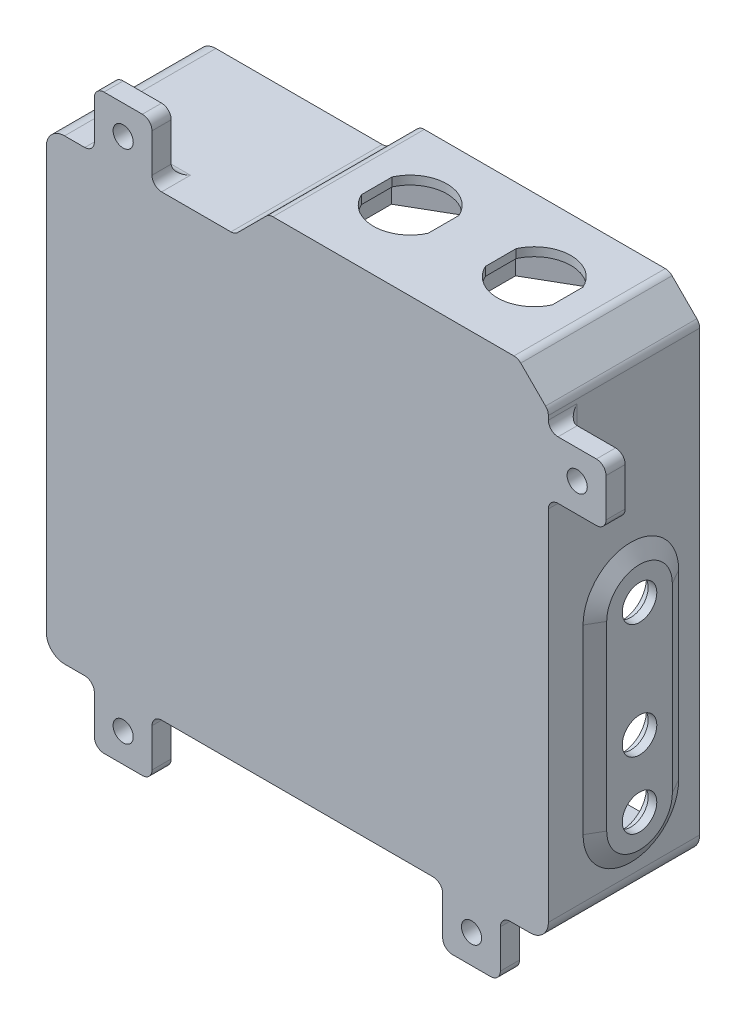
SolidWorks part; units mm, degrees
ref_plane "Front Plane" through (0, 0, 0) normal (0, 0, 1) x (1, 0, 0)
ref_plane "Top Plane" through (0, 0, 0) normal (0, 1, 0) x (1, 0, 0)
ref_plane "Right Plane" through (0, 0, 0) normal (1, 0, 0) x (0, 0, -1)
sketch "Sketch1" plane through (0, 0, 0) normal (0, 0, 1) x (1, 0, 0)
  line L9 (-68.5151, 31.874) -> (-68.5151, -49.766)
  line L10 (-31.5951, 31.874) -> (22.4049, 31.874)
  line L11 (22.4049, 31.874) -> (22.4049, -31.776)
  line L12 (22.4049, -31.776) -> (22.4049, -46.156)
  line L13 (22.4049, -46.156) -> (22.4049, -49.766)
  line L14 (-31.5951, -49.766) -> (-68.5151, -49.766)
  line L15 (22.4049, -49.766) -> (-31.5951, -49.766)
  line L16 (-31.5951, 36.874) -> (25.4049, 36.874)
  line L17 (-68.5151, 31.874) -> (-31.5951, 31.874)
  line L18 (27.4049, 34.874) -> (27.4049, -31.776)
  line L19 (27.4049, -31.776) -> (27.4049, -46.156)
  line L20 (27.4049, -46.156) -> (27.4049, -52.766)
  line L21 (25.4049, -54.766) -> (-31.5951, -54.766)
  line L22 (-31.5951, -54.766) -> (-71.5151, -54.766)
  line L23 (-73.5151, 34.874) -> (-73.5151, -52.766)
  line L24 (-71.5151, 36.874) -> (-31.5951, 36.874)
  line L25 (-31.5951, 36.874) -> (27.4049, 36.874) construction
  line L26 (27.4049, 36.874) -> (27.4049, -31.776) construction
  line L27 (27.4049, -46.156) -> (27.4049, -54.766) construction
  line L28 (27.4049, -54.766) -> (-31.5951, -54.766) construction
  line L29 (-31.5951, -54.766) -> (-73.5151, -54.766) construction
  line L30 (-73.5151, 36.874) -> (-73.5151, -54.766) construction
  line L31 (-73.5151, 36.874) -> (-31.5951, 36.874) construction
  line L32 (-71.5151, 38.674) -> (-31.5951, 38.674)
  line L33 (-31.5951, 38.674) -> (25.4049, 38.674)
  line L34 (29.2049, 34.874) -> (29.2049, -31.776)
  line L35 (29.2049, -31.776) -> (29.2049, -46.156)
  line L36 (29.2049, -46.156) -> (29.2049, -52.766)
  line L37 (25.4049, -56.566) -> (-31.5951, -56.566)
  line L38 (-31.5951, -56.566) -> (-71.5151, -56.566)
  line L39 (-75.3151, 34.874) -> (-75.3151, -52.766)
  arc A0 (25.4049, 36.874) -> (27.4049, 34.874) centre (25.4049, 34.874) cw
  arc A1 (27.4049, -52.766) -> (25.4049, -54.766) centre (25.4049, -52.766) cw
  arc A2 (-71.5151, -54.766) -> (-73.5151, -52.766) centre (-71.5151, -52.766) cw
  arc A3 (-73.5151, 34.874) -> (-71.5151, 36.874) centre (-71.5151, 34.874) cw
  arc A4 (25.4049, 38.674) -> (29.2049, 34.874) centre (25.4049, 34.874) cw
  arc A5 (29.2049, -52.766) -> (25.4049, -56.566) centre (25.4049, -52.766) cw
  arc A6 (-71.5151, -56.566) -> (-75.3151, -52.766) centre (-71.5151, -52.766) cw
  arc A7 (-75.3151, 34.874) -> (-71.5151, 38.674) centre (-71.5151, 34.874) cw
  dimension "D2" = 2
  dimension "D1" = 5
  dimension "D3" = 1.8
extrude "Boss-Extrude1" add sketch "Sketch1" along normal blind 1.5 contours L32 L33 A4 L34 L35 L36 A5 L37 L38 A6 L39 A7
sketch "Sketch2" plane through (0, 0, 1.5) normal (0, 0, 1) x (1, 0, 0)
  line L9 (-22.7084, 43.974) -> (-22.7084, 50.974)
  line L10 (-9.2084, 43.974) -> (-9.2084, 50.974)
  line L11 (3.1216, 43.974) -> (3.1216, 50.974)
  line L12 (16.6216, 43.974) -> (16.6216, 50.974)
  line L13 (18.8716, 41.674) -> (18.8716, 38.674)
  line L14 (0.8716, 41.674) -> (0.8716, 38.674)
  line L15 (-6.9584, 41.674) -> (-6.9584, 38.674)
  line L16 (-24.9584, 41.674) -> (-24.9584, 38.674)
  line L17 (-71.5151, 38.674) -> (25.4049, 38.674)
  line L18 (-22.7084, 43.974) -> (-24.9584, 43.974)
  line L19 (-24.9584, 43.974) -> (-24.9584, 41.674)
  line L20 (-9.2084, 43.974) -> (-6.9584, 43.974)
  line L21 (-6.9584, 43.974) -> (-6.9584, 41.674)
  line L22 (3.1216, 43.974) -> (0.8716, 43.974)
  line L23 (0.8716, 43.974) -> (0.8716, 41.674)
  line L24 (16.6216, 43.974) -> (18.8716, 43.974)
  line L25 (18.8716, 43.974) -> (18.8716, 41.674)
  line L26 (-22.7084, 45.774) -> (-24.9584, 45.774)
  line L27 (-9.2084, 45.774) -> (-6.9584, 45.774)
  line L28 (3.1216, 45.774) -> (0.8716, 45.774)
  line L29 (16.6216, 45.774) -> (18.8716, 45.774)
  line L30 (-24.9584, 45.774) -> (-28.9584, 45.774)
  line L31 (-28.9584, 45.774) -> (-36.0584, 38.674)
  line L32 (18.8716, 45.774) -> (22.8716, 45.774)
  line L33 (29.2049, 34.874) -> (29.2049, -52.766) construction
  line L34 (29.2049, 34.874) -> (29.2049, -52.766)
  line L35 (29.2049, 34.874) -> (29.2049, 39.4408)
  line L36 (-22.7084, 45.774) -> (-9.2084, 45.774)
  line L37 (22.8716, 45.774) -> (29.2049, 39.4408)
  line L38 (-6.9584, 45.774) -> (0.8716, 45.774)
  line L39 (3.1216, 45.774) -> (16.6216, 45.774)
  arc M10 (29.2049, 34.874) -> (25.4049, 38.674) centre (25.4049, 34.874) ccw
  line M11 (25.4049, 38.674) -> (-71.5151, 38.674)
  dimension "D1" = 1.8
  dimension "D2" = 1.8
  dimension "D3" = 1.8
  dimension "D4" = 1.8
extrude "Boss-Extrude2" add sketch "Sketch2" against normal blind 1.5 separate body contours L30 L31 L16 L19 L18 L9 L26 M11 | L36 L9 L18 L19 L16 L15 L21 L20 L10 M11 | L38 L27 L10 L20 L21 L15 L14 L23 L22 L11 L28 M11 | L39 L11 L22 L23 L14 L13 L25 L24 L12 M11 | L37 L32 L29 L12 L24 L25 L13 L35 M11 M10 region at (-28.6478, 41.8928, 1.5) region at (-15.9584, 42.0447, 1.5) region at (-3.0434, 42.561, 1.5) region at (9.8716, 42.0447, 1.5) region at (22.8246, 41.6987, 1.5)
fillet "Fillet1" radius 2 4 edges at (22.8716, 45.774, 0.75) (29.2049, 39.4408, 0.75) (-28.9584, 45.774, 0.75) (-36.0584, 38.674, 0.75)
sketch "Sketch3" plane through (0, 0, 0) normal (0, 0, -1) x (-1, 0, 0)
  line L0 (-29.2049, 38.6123) -> (-29.2049, -52.766) construction
  line L1 (-23.4574, 45.1882) -> (-28.6191, 40.0265) construction
  line L2 (-22.0432, 45.774) -> (28.1299, 45.774) construction
  line L3 (29.5442, 45.1882) -> (35.4726, 39.2598) construction
  line L4 (71.5151, 38.674) -> (36.8868, 38.674) construction
  line L5 (75.3151, 34.874) -> (75.3151, -52.766) construction
  line L6 (-25.4049, -56.566) -> (71.5151, -56.566) construction
  line L7 (-29.2049, 38.6123) -> (-29.2049, -52.766)
  line L8 (-23.4574, 45.1882) -> (-28.6191, 40.0265)
  line L9 (-22.0432, 45.774) -> (28.1299, 45.774)
  line L10 (29.5442, 45.1882) -> (35.4726, 39.2598)
  line L11 (71.5151, 38.674) -> (36.8868, 38.674)
  line L12 (75.3151, 34.874) -> (75.3151, -52.766)
  line L13 (-25.4049, -56.566) -> (71.5151, -56.566)
  line L14 (-25.4049, -54.766) -> (71.5151, -54.766)
  line L15 (73.5151, 34.874) -> (73.5151, -52.766)
  line L16 (71.5151, 36.874) -> (36.8868, 36.874)
  line L17 (28.2714, 43.9154) -> (34.1998, 37.987)
  line L18 (-22.0432, 43.974) -> (28.1299, 43.974)
  line L19 (-22.1846, 43.9154) -> (-27.3463, 38.7538)
  line L20 (-27.4049, 38.6123) -> (-27.4049, -52.766)
  arc A0 (-29.2049, -52.766) -> (-25.4049, -56.566) centre (-25.4049, -52.766) ccw construction
  arc A1 (-28.6191, 40.0265) -> (-29.2049, 38.6123) centre (-27.2049, 38.6123) ccw construction
  arc A2 (-22.0432, 45.774) -> (-23.4574, 45.1882) centre (-22.0432, 43.774) ccw construction
  arc A3 (29.5442, 45.1882) -> (28.1299, 45.774) centre (28.1299, 43.774) ccw construction
  arc A4 (35.4726, 39.2598) -> (36.8868, 38.674) centre (36.8868, 40.674) ccw construction
  arc A5 (75.3151, 34.874) -> (71.5151, 38.674) centre (71.5151, 34.874) ccw construction
  arc A6 (71.5151, -56.566) -> (75.3151, -52.766) centre (71.5151, -52.766) ccw construction
  arc A7 (-29.2049, -52.766) -> (-25.4049, -56.566) centre (-25.4049, -52.766) ccw
  arc A8 (-28.6191, 40.0265) -> (-29.2049, 38.6123) centre (-27.2049, 38.6123) ccw
  arc A9 (-22.0432, 45.774) -> (-23.4574, 45.1882) centre (-22.0432, 43.774) ccw
  arc A10 (29.5442, 45.1882) -> (28.1299, 45.774) centre (28.1299, 43.774) ccw
  arc A11 (35.4726, 39.2598) -> (36.8868, 38.674) centre (36.8868, 40.674) ccw
  arc A12 (75.3151, 34.874) -> (71.5151, 38.674) centre (71.5151, 34.874) ccw
  arc A13 (71.5151, -56.566) -> (75.3151, -52.766) centre (71.5151, -52.766) ccw
  arc A14 (71.5151, -54.766) -> (73.5151, -52.766) centre (71.5151, -52.766) ccw
  arc A15 (73.5151, 34.874) -> (71.5151, 36.874) centre (71.5151, 34.874) ccw
  arc A16 (34.1998, 37.987) -> (36.8868, 36.874) centre (36.8868, 40.674) ccw
  arc A17 (28.2714, 43.9154) -> (28.1299, 43.974) centre (28.1299, 43.774) ccw
  arc A18 (-22.0432, 43.974) -> (-22.1846, 43.9154) centre (-22.0432, 43.774) ccw
  arc A19 (-27.3463, 38.7538) -> (-27.4049, 38.6123) centre (-27.2049, 38.6123) ccw
  arc A20 (-27.4049, -52.766) -> (-25.4049, -54.766) centre (-25.4049, -52.766) ccw
  line M2 (28.1299, 45.774) -> (-22.0432, 45.774)
  arc M3 (-22.0432, 45.774) -> (-23.4574, 45.1882) centre (-22.0432, 43.774) ccw
  line M4 (-23.4574, 45.1882) -> (-28.6191, 40.0265)
  arc M5 (-28.6191, 40.0265) -> (-29.2049, 38.6123) centre (-27.2049, 38.6123) ccw
  line M6 (-29.2049, 38.6123) -> (-29.2049, -52.766)
  arc M7 (-29.2049, -52.766) -> (-25.4049, -56.566) centre (-25.4049, -52.766) ccw
  line M8 (-25.4049, -56.566) -> (71.5151, -56.566)
  arc M9 (71.5151, -56.566) -> (75.3151, -52.766) centre (71.5151, -52.766) ccw
  line M10 (75.3151, -52.766) -> (75.3151, 34.874)
  arc M11 (75.3151, 34.874) -> (71.5151, 38.674) centre (71.5151, 34.874) ccw
  line M12 (71.5151, 38.674) -> (36.8868, 38.674)
  arc M13 (36.8868, 38.674) -> (35.4726, 39.2598) centre (36.8868, 40.674) cw
  line M14 (35.4726, 39.2598) -> (29.5442, 45.1882)
  arc M15 (29.5442, 45.1882) -> (28.1299, 45.774) centre (28.1299, 43.774) ccw
  dimension "D1" = 1.8
extrude "Boss-Extrude3" add sketch "Sketch3" along normal blind 30 contours A20 L20 A19 L19 A18 L18 A17 L17 A16 L16 A15 L15 A14 L14 M15 M2 M3 M4 M5 M6 M7 M8 M9 M10 M11 M12 M13 M14 region at (27.7012, 38.8179, 0)
sketch "Sketch5" plane through (29.2049, 0, 0) normal (1, 0, 0) x (0, 0, -1)
  line L4 (-1.5, -52.766) -> (30, -52.766)
  line L5 (30, -52.766) -> (30, 38.6123)
  line L6 (30, 38.6123) -> (-1.5, 38.6123)
  line L7 (-1.5, 38.6123) -> (-1.5, -52.766)
  line L8 (-1.5, -52.766) -> (30, -52.766)
  line L9 (30, -52.766) -> (30, 38.6123)
  line L10 (30, 38.6123) -> (-1.5, 38.6123)
  line L11 (-1.5, 38.6123) -> (-1.5, -52.766)
  circle A1 centre (15.675, -40.576) radius 4.832
  circle A3 centre (15.675, -26.676) radius 4.832
  circle A5 centre (15.675, -2.776) radius 4.832
  circle A6 centre (15.675, -40.576) radius 5.032
  circle A7 centre (15.675, -26.676) radius 5.032
  circle A8 centre (15.675, -2.776) radius 5.032
  dimension "D1" = 0
  dimension "D2" = 0.2
extrude "Cut-Extrude1" cut sketch "Sketch5" against normal blind 10 contours A6 A1 | A1 | A7 A3 | A3 | A8 A5 | A5 region at (29.2049, -40.576, -15.675) region at (29.2049, -26.676, -15.675) region at (29.2049, -2.776, -15.675) region at (29.2049, -40.576, -10.7853) region at (29.2049, -26.676, -10.7853) region at (29.2049, -2.776, -10.7853)
sketch "Sketch6" plane through (29.2049, 0, 0) normal (1, 0, 0) x (0, 0, -1)
  line L2 (8.843, -40.576) -> (8.843, -2.776)
  line L3 (22.507, -40.576) -> (22.507, -2.776)
  circle A0 centre (15.675, -2.776) radius 5.032 construction
  circle A1 centre (15.675, -40.576) radius 5.032 construction
  circle A2 centre (15.675, -40.576) radius 3.597
  circle A3 centre (15.675, -26.676) radius 3.597
  arc A4 (22.507, -2.776) -> (8.843, -2.776) centre (15.675, -2.776) ccw
  arc A5 (8.843, -40.576) -> (22.507, -40.576) centre (15.675, -40.576) ccw
  arc A7 (20.707, -2.776) -> (10.643, -2.776) centre (15.675, -2.776) ccw
  circle A8 centre (15.675, -2.776) radius 3.597
  arc A9 (10.643, -40.576) -> (20.707, -40.576) centre (15.675, -40.576) ccw
  circle A15 centre (15.675, -2.776) radius 3.397
  circle A16 centre (15.675, -26.676) radius 3.397
  circle A17 centre (15.675, -40.576) radius 3.397
  circle M3 centre (15.675, -26.676) radius 5.032
  circle M4 centre (15.675, -2.776) radius 5.032
  circle M5 centre (15.675, -40.576) radius 5.032
  dimension "D1" = 0.2
extrude "Boss-Extrude4" add sketch "Sketch6" along normal blind 1.8 contours L2 A5 L3 A4 M3 M5 M4 | A2 M5 | A8 M4 | A3 M3 region at (29.2049, -20.739, -15.675) region at (29.2049, -7.6657, -15.675) region at (29.2049, -35.6863, -15.675) region at (29.2049, -26.676, -10.7853)
chamfer "Chamfer1" distance 1.8 angle 60 4 edges at (29.2049, -21.676, -8.843) (29.2049, -47.408, -15.675) (29.2049, 4.056, -15.675) (29.2049, -21.676, -22.507) first distance on face at (30.1049, -21.676, -8.843) first distance on face at (30.1049, -43.992, -15.675) first distance on face at (30.1049, 0.64, -15.675) first distance on face at (30.1049, -21.676, -22.507)
sketch "Sketch7" plane through (0, 45.774, 0) normal (0, 1, 0) x (1, 0, 0)
  line L8 (3.1216, 14.8923) -> (3.1216, 11.7395)
  line L9 (3.1216, 14.8923) -> (3.1216, 18.0451)
  line L10 (16.6216, 14.8923) -> (16.6216, 11.7395)
  line L11 (16.6216, 14.8923) -> (16.6216, 18.0451)
  line L12 (-9.2084, 14.8923) -> (-9.2084, 11.7395)
  line L13 (-9.2084, 14.8923) -> (-9.2084, 18.0451)
  line L14 (-22.7084, 14.8923) -> (-22.7084, 11.7395)
  line L15 (-22.7084, 14.8923) -> (-22.7084, 18.0451)
  line L16 (-22.9084, 14.8923) -> (-22.9084, 18.0892)
  line L17 (-22.9084, 14.8923) -> (-22.9084, 11.6954)
  line L18 (-9.0084, 14.8923) -> (-9.0084, 11.6954)
  line L19 (-9.0084, 14.8923) -> (-9.0084, 18.0892)
  line L20 (2.9216, 14.8923) -> (2.9216, 18.0892)
  line L21 (2.9216, 14.8923) -> (2.9216, 11.6954)
  line L22 (16.8216, 14.8923) -> (16.8216, 11.6954)
  line L23 (16.8216, 14.8923) -> (16.8216, 18.0892)
  arc A4 (3.1216, 11.7395) -> (16.6216, 11.7395) centre (9.8716, 14.8923) ccw
  arc A5 (16.6216, 18.0451) -> (3.1216, 18.0451) centre (9.8716, 14.8923) ccw
  arc A6 (-22.7084, 11.7395) -> (-9.2084, 11.7395) centre (-15.9584, 14.8923) ccw
  arc A7 (-9.2084, 18.0451) -> (-22.7084, 18.0451) centre (-15.9584, 14.8923) ccw
  arc A8 (-9.0084, 18.0892) -> (-22.9084, 18.0892) centre (-15.9584, 14.8923) ccw
  arc A9 (-22.9084, 11.6954) -> (-9.0084, 11.6954) centre (-15.9584, 14.8923) ccw
  arc A10 (16.8216, 18.0892) -> (2.9216, 18.0892) centre (9.8716, 14.8923) ccw
  arc A11 (2.9216, 11.6954) -> (16.8216, 11.6954) centre (9.8716, 14.8923) ccw
  dimension "D1" = 0.2
extrude "Cut-Extrude2" cut sketch "Sketch7" against normal blind 11.8 contours L17 A9 L18 L19 A8 L16 A7 L13 L12 A6 L14 L15 | L13 A7 L15 L14 A6 L12 | L21 A11 L22 L23 A10 L20 A5 L11 L10 A4 L8 L9 | L11 A5 L9 L8 A4 L10 region at (9.8716, 45.774, -14.8923) region at (-15.9584, 45.774, -14.8923) region at (-22.8877, 45.774, -16.4907) region at (2.9423, 45.774, -16.4907)
sketch "Sketch8" plane through (0, 43.974, 0) normal (0, -1, 0) x (1, 0, 0)
  line L14 (-15.9584, -4.5) -> (-24.9584, -9.6962)
  line L15 (-24.9584, -9.6962) -> (-24.9584, -20.0885)
  line L16 (-24.9584, -20.0885) -> (-15.9584, -25.2846)
  line L17 (-15.9584, -25.2846) -> (-6.9584, -20.0885)
  line L18 (-6.9584, -20.0885) -> (-6.9584, -9.6962)
  line L19 (-6.9584, -9.6962) -> (-15.9584, -4.5)
  line L20 (9.8716, -4.5) -> (0.8716, -9.6962)
  line L21 (0.8716, -9.6962) -> (0.8716, -20.0885)
  line L22 (0.8716, -20.0885) -> (9.8716, -25.2846)
  line L23 (9.8716, -25.2846) -> (18.8716, -20.0885)
  line L24 (18.8716, -20.0885) -> (18.8716, -9.6962)
  line L25 (18.8716, -9.6962) -> (9.8716, -4.5)
  line L26 (-28.1299, -30) -> (-28.1299, 0)
  line L27 (22.0432, -30) -> (22.0432, 0)
  line L28 (22.0432, 0) -> (-28.1299, 0) construction
  line L29 (22.0432, -30) -> (-28.1299, -30) construction
  line L30 (22.0432, 0) -> (-28.1299, 0)
  line L31 (22.0432, -30) -> (-28.1299, -30)
  line L32 (0.6716, -20.2039) -> (9.8716, -25.5155)
  line L33 (9.8716, -25.5155) -> (19.0716, -20.2039)
  line L34 (19.0716, -20.2039) -> (19.0716, -9.5807)
  line L35 (19.0716, -9.5807) -> (9.8716, -4.2691)
  line L36 (9.8716, -4.2691) -> (0.6716, -9.5807)
  line L37 (0.6716, -9.5807) -> (0.6716, -20.2039)
  line L38 (-15.9584, -25.5155) -> (-6.7584, -20.2039)
  line L39 (-6.7584, -20.2039) -> (-6.7584, -9.5807)
  line L40 (-6.7584, -9.5807) -> (-15.9584, -4.2691)
  line L41 (-15.9584, -4.2691) -> (-25.1584, -9.5807)
  line L42 (-25.1584, -9.5807) -> (-25.1584, -20.2039)
  line L43 (-25.1584, -20.2039) -> (-15.9584, -25.5155)
  line M11 (22.0432, 0) -> (-28.1299, 0)
  line M12 (-28.1299, 0) -> (-28.1299, -30)
  line M13 (-28.1299, -30) -> (22.0432, -30)
  line M14 (22.0432, -30) -> (22.0432, 0)
  dimension "D1" = 0.2
extrude "Boss-Extrude5" add sketch "Sketch8" along normal up to surface (5.3 mm away) contours L43 L42 L41 L40 L39 L38 L37 L36 L35 L34 L33 L32 M14 M11 M12 M13 region at (-3.0434, 43.974, -15.0687)
sketch "Sketch9" plane through (0, 0, -30) normal (0, 0, -1) x (-1, 0, 0)
  line L0 (28.2714, 43.9154) -> (34.1998, 37.987) construction
  line L1 (28.1299, 38.674) -> (28.1299, 43.974) construction
  line L2 (-27.4049, 38.6123) -> (-27.4049, -52.766) construction
  line L3 (-22.0432, 38.674) -> (-22.0432, 43.974) construction
  line L4 (-22.1846, 43.9154) -> (-27.3463, 38.7538) construction
  line L5 (28.2714, 43.9154) -> (34.1998, 37.987)
  line L6 (28.1299, 38.674) -> (28.1299, 43.974)
  line L7 (-27.4049, 38.6123) -> (-27.4049, -52.766)
  line L8 (-22.0432, 38.674) -> (-22.0432, 43.974)
  line L9 (-22.1846, 43.9154) -> (-27.3463, 38.7538)
  line L10 (-22.0432, 38.674) -> (-27.3951, 38.674)
  line L11 (28.1299, 38.674) -> (33.5128, 38.674)
  arc A0 (34.1998, 37.987) -> (36.8868, 36.874) centre (36.8868, 40.674) ccw construction
  arc A1 (34.1998, 37.987) -> (36.8868, 36.874) centre (36.8868, 40.674) ccw
  arc A2 (-27.3463, 38.7538) -> (-27.4049, 38.6123) centre (-27.2049, 38.6123) ccw construction
  arc M3 (-27.4049, 38.6123) -> (-27.3463, 38.7538) centre (-27.2049, 38.6123) cw
  line M4 (-27.3463, 38.7538) -> (-22.1846, 43.9154)
  arc M5 (-22.1846, 43.9154) -> (-22.0432, 43.974) centre (-22.0432, 43.774) cw
  line M6 (-22.0432, 43.974) -> (-22.0432, 38.674)
  line M8 (28.1299, 38.674) -> (28.1299, 43.974)
  arc M9 (28.1299, 43.974) -> (28.2714, 43.9154) centre (28.1299, 43.774) cw
  line M10 (28.2714, 43.9154) -> (34.1998, 37.987)
extrude "Boss-Extrude6" add sketch "Sketch9" against normal up to surface (30 mm away) separate body contours L10 M6 M5 M4 M3 | L11 M8 M10 M9 region at (-29.9247, 40.4672, -30) region at (23.8378, 40.4673, -30) up to face at (-17.0085, 16.3369, 0)
fillet "Fillet2" radius 2 2 edges at (-33.5128, 38.674, -15) (27.3951, 38.674, -15)
sketch "Sketch10" plane through (0, 0, 0) normal (0, 0, -1) x (-1, 0, 0)
  circle A16 centre (65.0151, 9.644) radius 1.5
  circle A17 centre (35.6451, -31.586) radius 1.5
  circle A18 centre (35.6451, -3.706) radius 1.5
  circle A19 centre (35.6451, 24.174) radius 1.5
  circle A20 centre (25.9851, -46.156) radius 1.5
  circle A21 centre (-18.7949, -46.156) radius 1.5
  circle A22 centre (-18.7949, -31.776) radius 1.5
  circle A23 centre (25.9851, -31.776) radius 1.5
  circle A24 centre (25.9851, -22.556) radius 1.5
  circle A25 centre (25.9851, -8.176) radius 1.5
  circle A26 centre (-18.7949, -22.556) radius 1.5
  circle A27 centre (-18.7949, -8.176) radius 1.5
  circle A28 centre (-18.7949, 1.044) radius 1.5
  circle A29 centre (25.9851, 1.044) radius 1.5
  circle A30 centre (25.9851, 15.424) radius 1.5
  circle A31 centre (-18.7949, 15.424) radius 1.5
  circle A34 centre (65.0151, -46.116) radius 1.5
  circle A35 centre (65.0151, -18.236) radius 1.5
  circle A36 centre (-18.7949, 15.424) radius 2.85
  circle A37 centre (25.9851, 15.424) radius 2.85
  circle A38 centre (25.9851, 1.044) radius 2.85
  circle A39 centre (-18.7949, 1.044) radius 2.85
  circle A40 centre (-18.7949, -8.176) radius 2.85
  circle A41 centre (25.9851, -8.176) radius 2.85
  circle A42 centre (25.9851, -22.556) radius 2.85
  circle A43 centre (-18.7949, -22.556) radius 2.85
  circle A44 centre (-18.7949, -31.776) radius 2.85
  circle A45 centre (25.9851, -31.776) radius 2.85
  circle A46 centre (25.9851, -46.156) radius 2.85
  circle A47 centre (-18.7949, -46.156) radius 2.85
  circle A48 centre (35.6451, -3.706) radius 2.85
  circle A49 centre (35.6451, 24.174) radius 2.85
  circle A50 centre (65.0151, 9.644) radius 2.85
  circle A51 centre (65.0151, -18.236) radius 2.85
  circle A52 centre (35.6451, -31.586) radius 2.85
  circle A53 centre (65.0151, -46.116) radius 2.85
  dimension "D1" = 1.35
extrude "Boss-Extrude7" add sketch "Sketch10" along normal up to surface (9 mm away)
chamfer "Chamfer2" distance 2 angle 45 18 edges at (-67.8651, -46.116, 0) (-67.8651, -18.236, 0) (-67.8651, 9.644, 0) (-38.4951, -31.586, 0) (-38.4951, -3.706, 0) (-38.4951, 24.174, 0) (-28.8351, -46.156, 0) (15.9449, -46.156, 0) (15.9449, -31.776, 0) (-28.8351, -31.776, 0) (-28.8351, -22.556, 0) (15.9449, -22.556, 0) (15.9449, -8.176, 0) (-28.8351, -8.176, 0) (-28.8351, 1.044, 0) (-28.8351, 15.424, 0) (15.9449, 1.044, 0) (15.9449, 15.424, 0)
sketch "Sketch11" plane through (0, 0, 0) normal (0, 0, -1) x (-1, 0, 0)
  line L0 (71.5151, 36.874) -> (36.8868, 36.874) construction
  line L1 (73.5151, 34.874) -> (73.5151, -52.766) construction
  line L2 (-25.4049, -54.766) -> (71.5151, -54.766) construction
  line L3 (-27.4049, 36.674) -> (-27.4049, -52.766) construction
  line L4 (-25.4049, 38.674) -> (32.6844, 38.674) construction
  line L5 (71.5151, 36.874) -> (36.8868, 36.874)
  line L6 (73.5151, 34.874) -> (73.5151, -52.766)
  line L7 (-25.4049, -54.766) -> (71.5151, -54.766)
  line L8 (-27.4049, 36.674) -> (-27.4049, -52.766)
  line L9 (-25.4049, 38.674) -> (32.6844, 38.674)
  arc A0 (34.0986, 38.0882) -> (32.6844, 38.674) centre (32.6844, 36.674) ccw construction
  arc A1 (34.1998, 37.987) -> (36.8868, 36.874) centre (36.8868, 40.674) ccw construction
  arc A2 (73.5151, 34.874) -> (71.5151, 36.874) centre (71.5151, 34.874) ccw construction
  arc A3 (71.5151, -54.766) -> (73.5151, -52.766) centre (71.5151, -52.766) ccw construction
  arc A4 (-27.4049, -52.766) -> (-25.4049, -54.766) centre (-25.4049, -52.766) ccw construction
  arc A5 (-25.4049, 38.674) -> (-27.4049, 36.674) centre (-25.4049, 36.674) ccw construction
  arc A6 (34.0986, 38.0882) -> (32.6844, 38.674) centre (32.6844, 36.674) ccw
  arc A7 (34.1998, 37.987) -> (36.8868, 36.874) centre (36.8868, 40.674) ccw
  arc A8 (73.5151, 34.874) -> (71.5151, 36.874) centre (71.5151, 34.874) ccw
  arc A9 (71.5151, -54.766) -> (73.5151, -52.766) centre (71.5151, -52.766) ccw
  arc A10 (-27.4049, -52.766) -> (-25.4049, -54.766) centre (-25.4049, -52.766) ccw
  arc A11 (-25.4049, 38.674) -> (-27.4049, 36.674) centre (-25.4049, 36.674) ccw
  circle A12 centre (-25.4049, -52.766) radius 1.5
  circle A13 centre (71.5151, -52.766) radius 1.5
  circle A14 centre (23.0551, -52.766) radius 1.5
  circle A15 centre (-25.4049, 36.674) radius 1.5
  circle A16 centre (71.5151, 34.874) radius 1.5
  circle A17 centre (32.6844, 36.674) radius 1.5
  circle A18 centre (71.5151, -8.946) radius 1.5
  circle A19 centre (-25.4049, -15.8847) radius 1.5
  circle A20 centre (-25.4049, 36.674) radius 2.85
  circle A21 centre (32.6844, 36.674) radius 2.85
  circle A22 centre (71.5151, 34.874) radius 2.85
  circle A23 centre (71.5151, -8.946) radius 2.85
  circle A24 centre (71.5151, -52.766) radius 2.85
  circle A25 centre (23.0551, -52.766) radius 2.85
  circle A26 centre (-25.4049, -52.766) radius 2.85
  circle A27 centre (-25.4049, -15.8847) radius 2.85
  circle M6 centre (25.9851, -46.156) radius 4.85
  line M28 (34.1998, 37.987) -> (34.0986, 38.0882)
  arc M29 (34.0986, 38.0882) -> (32.6844, 38.674) centre (32.6844, 36.674) ccw
  line M30 (32.6844, 38.674) -> (-25.4049, 38.674)
  arc M31 (-25.4049, 38.674) -> (-27.4049, 36.674) centre (-25.4049, 36.674) ccw
  line M32 (-27.4049, 36.674) -> (-27.4049, -52.766)
  arc M33 (-27.4049, -52.766) -> (-25.4049, -54.766) centre (-25.4049, -52.766) ccw
  line M34 (-25.4049, -54.766) -> (71.5151, -54.766)
  arc M35 (71.5151, -54.766) -> (73.5151, -52.766) centre (71.5151, -52.766) ccw
  line M36 (73.5151, -52.766) -> (73.5151, 34.874)
  arc M37 (73.5151, 34.874) -> (71.5151, 36.874) centre (71.5151, 34.874) ccw
  line M38 (71.5151, 36.874) -> (36.8868, 36.874)
  dimension "D1" = 1.35
  dimension "D2" = 1.35
extrude "Boss-Extrude8" add sketch "Sketch11" along normal up to surface (30 mm away) contours A20 L9 A15 M32 M31 | L9 A20 M32 M31 | A21 A7 A17 M30 M28 M29 | A7 A21 M30 M29 M28 | A22 L6 A16 M38 M37 | L6 A22 M38 M37 | L6 A23 | L6 A23 A18 | L7 A24 M36 M35 | A24 L7 A13 M36 M35 | A25 L7 A14 M6 | L7 A25 | A26 M32 M34 M33 | A26 A12 M34 M32 M33 | A27 A19 M32 | A27 M32 | A25 M6 region at (-72.8809, 36.2397, 0) region at (-70.4999, 36.943, 0) region at (-35.4503, 36.9004, 0) region at (-33.3814, 38.6778, 0) region at (-73.8599, -8.946, 0) region at (-73.4403, -8.946, 0) region at (22.8312, 37.7287, 0) region at (24.3897, 38.743, 0) region at (-74.0804, -51.6921, 0) region at (-73.4466, -51.7508, 0) region at (24.3332, -13.3248, 0) region at (27.7496, -15.8847, 0) region at (-23.0551, -55.1108, 0) region at (-23.0551, -54.6912, 0) region at (24.3308, -50.2004, 0) region at (27.4739, -51.7508, 0) region at (-24.1099, -50.3865, 0) up to face at (-26.8549, 6.9607, -30)
fillet "Fillet3" radius 2 16 edges at (-35.4964, 37.1375, -15) (-30.654, 38.674, -15) (-69.4848, 36.874, -15) (-73.5151, 32.8436, -15) (-73.5151, -10.9764, -15) (-73.5151, -6.9156, -15) (-73.5151, -50.7356, -15) (-69.4848, -54.766, -15) (-21.0248, -54.766, -15) (-25.0855, -54.766, -15) (27.4049, -50.7356, -15) (23.3745, -54.766, -15) (27.4049, -13.8543, -15) (27.4049, -17.9151, -15) (27.4049, 34.6436, -15) (23.3745, 38.674, -15)
sketch "Sketch12" plane through (0, 0, 1.5) normal (0, 0, 1) x (1, 0, 0)
  line L0 (29.2049, 38.6123) -> (29.2049, -52.766) construction
  line L1 (-75.3151, 34.874) -> (-75.3151, -52.766) construction
  line L2 (25.4049, -56.566) -> (-71.5151, -56.566) construction
  line L3 (-71.5151, 38.674) -> (-36.8868, 38.674) construction
  line L4 (29.2049, 38.6123) -> (29.2049, -52.766)
  line L5 (-75.3151, 34.874) -> (-75.3151, -52.766)
  line L6 (25.4049, -56.566) -> (-71.5151, -56.566)
  line L7 (-71.5151, 38.674) -> (-36.8868, 38.674)
  line L8 (-65.3151, -56.566) -> (-65.3151, -68.566)
  line L9 (-65.3151, -68.566) -> (-53.3151, -68.566)
  line L10 (-53.3151, -68.566) -> (-53.3151, -56.566)
  line L11 (19.2049, -56.566) -> (19.2049, -68.566)
  line L12 (19.2049, -68.566) -> (7.2049, -68.566)
  line L13 (7.2049, -68.566) -> (7.2049, -56.566)
  line L14 (-65.3151, 38.674) -> (-65.3151, 50.674)
  line L15 (-65.3151, 50.674) -> (-53.3151, 50.674)
  line L16 (-53.3151, 50.674) -> (-53.3151, 38.674)
  line L17 (29.2049, 35.774) -> (41.2049, 35.774)
  line L18 (41.2049, 35.774) -> (41.2049, 23.774)
  line L19 (41.2049, 23.774) -> (29.2049, 23.774)
  line L20 (22.0432, 45.774) -> (-28.1299, 45.774) construction
  circle A0 centre (-59.3151, -62.566) radius 2.1
  circle A1 centre (13.2049, -62.566) radius 2.1
  circle A2 centre (-59.3151, 44.674) radius 2.1
  circle A3 centre (35.2049, 29.774) radius 2.1
  dimension "D7" = 10
  dimension "D1" = 10
  dimension "D2" = 12
  dimension "D3" = 12
  dimension "D4" = 10
  dimension "D5" = 12
  dimension "D6" = 12
  dimension "D8" = 12
  dimension "D9" = 12
  dimension "D10" = 6
  dimension "D11" = 6
extrude "Boss-Extrude9" add sketch "Sketch12" against normal blind 4 contours L16 L15 L14 L7 A2 | L9 L10 L6 L8 A0 | L13 L12 L11 L6 A1 | L19 L18 L17 L4 A3 region at (35.2049, 35.6043, 1.5) region at (19.0351, -62.566, 1.5) region at (-53.4849, -62.566, 1.5) region at (-65.1454, 44.674, 1.5)
fillet "Fillet4" radius 2 12 edges at (-65.3151, 38.674, -0.5) (-59.3151, 38.674, -2.5) (-53.3151, 38.674, -0.5) (29.2049, 35.774, -0.5) (29.2049, 23.774, -0.5) (29.2049, 29.774, -2.5) (-53.3151, -56.566, -0.5) (-65.3151, -56.566, -0.5) (-59.3151, -56.566, -2.5) (7.2049, -56.566, -0.5) (13.2049, -56.566, -2.5) (19.2049, -56.566, -0.5)
fillet "Fillet5" radius 2 8 edges at (-65.3151, -68.566, -0.5) (-53.3151, -68.566, -0.5) (7.2049, -68.566, -0.5) (19.2049, -68.566, -0.5) (41.2049, 23.774, -0.5) (41.2049, 35.774, -0.5) (-65.3151, 50.674, -0.5) (-53.3151, 50.674, -0.5)
